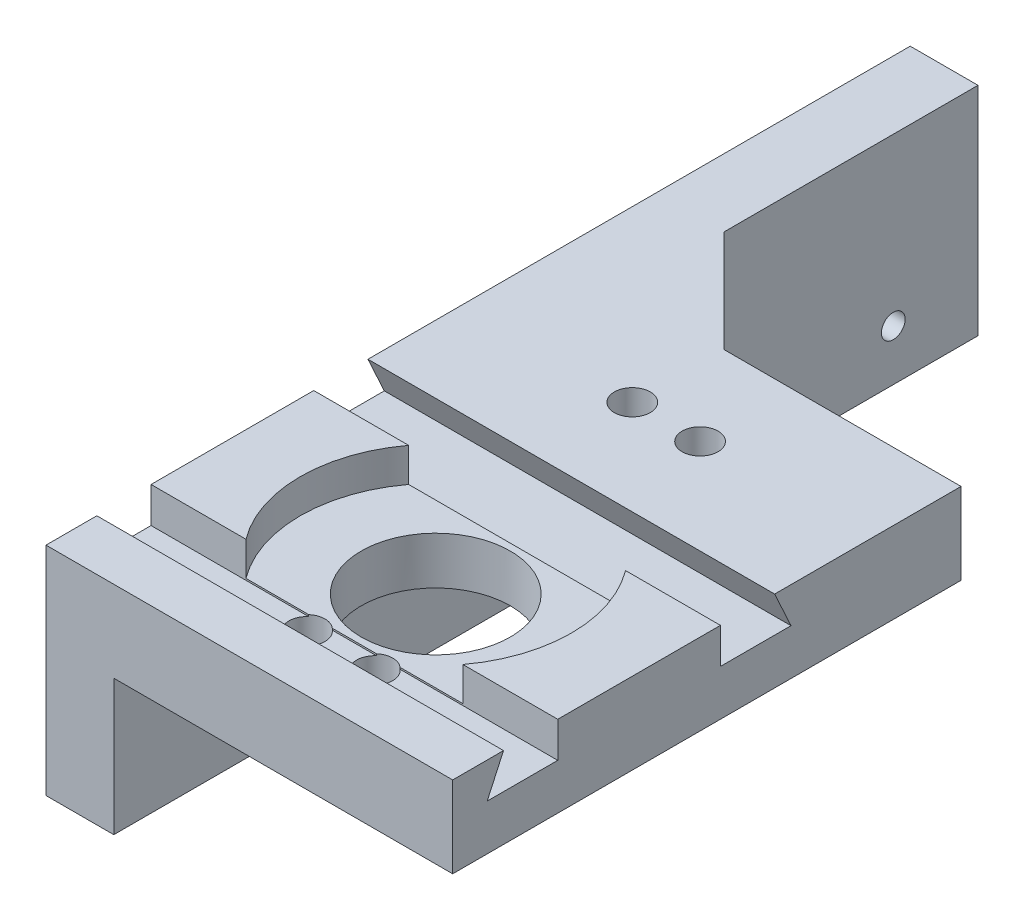
SolidWorks part; units mm, degrees
ref_plane "Front Plane" through (0, 0, 0) normal (0, 0, 1) x (1, 0, 0)
ref_plane "Top Plane" through (0, 0, 0) normal (0, 1, 0) x (1, 0, 0)
ref_plane "Right Plane" through (0, 0, 0) normal (1, 0, 0) x (0, 0, -1)
sketch "Sketch1" plane through (0, 0, 0) normal (0, 1, 0) x (1, 0, 0)
  line L1 (-30, -37.5) -> (30, -37.5)
  line L2 (-30, -37.5) -> (-30, 37.5)
  line L3 (-30, 37.5) -> (30, 37.5)
  line L4 (30, -37.5) -> (30, 37.5)
  line L5 (-30, -37.5) -> (30, 37.5) construction
  line L6 (-30, 37.5) -> (30, -37.5) construction
  point P0 (0, 0)
  dimension "D1" = 75
  dimension "D2" = 60
extrude "Boss-Extrude1" add sketch "Sketch1" along normal blind 12
sketch "Sketch6" plane through (0, 0, 0) normal (0, -1, 0) x (1, 0, 0)
  line L0 (0, 0) -> (0, 24.5997) construction
  line L1 (-10, -28) -> (10, -28)
  line L2 (-10, -28) -> (-10, -20)
  line L3 (-10, -20) -> (10, -20)
  line L4 (10, -28) -> (10, -20)
  line L5 (0, 0) -> (-22.4424, 0) construction
  line L6 (10, 28) -> (10, 20)
  line L7 (-10, 20) -> (10, 20)
  line L8 (-10, 28) -> (-10, 20)
  line L9 (-10, 28) -> (10, 28)
  line L11 (-1.25, -28) -> (1.25, -28)
  line L12 (-1.25, -28) -> (-1.25, 28)
  line L13 (-1.25, 28) -> (1.25, 28)
  line L14 (1.25, -28) -> (1.25, 28)
  circle A0 centre (5, -24) radius 2.4658 construction
  circle A1 centre (-5, -24) radius 2.4658 construction
  circle A2 centre (-5, 24) radius 2.4658 construction
  circle A3 centre (5, 24) radius 2.4658 construction
  point P13 (10, -24)
  dimension "D1" = 10
  dimension "D2" = 5
  dimension "D3" = 4
  dimension "D4" = 48
  dimension "D5" = 2.5
extrude "Boss-Extrude2" add sketch "Sketch6" along normal blind 9 contours L1 L12 L3 L2 | L14 L1 L4 L3 | L14 L7 L6 L9 | L7 L12 L9 L8 region at (-5.625, 0, -24) region at (5.625, 0, -24) region at (-5.625, 0, 24) region at (5.625, 0, 24)
sketch "Sketch3" plane through (0, 12, 0) normal (0, 1, 0) x (1, 0, 0)
  line L0 (-31.5126, 0) -> (79.6914, 0) construction
  line L1 (0, 43.6018) -> (0, -26.5157) construction
  circle A0 centre (-5, 24) radius 2.65
  circle A1 centre (5, 24) radius 2.65
  circle A2 centre (5, -24) radius 2.65
  circle A3 centre (-5, -24) radius 2.65
  circle A4 centre (0, -10) radius 11
  dimension "D1" = 5.3
  dimension "D5" = 22
  dimension "D2" = 10
  dimension "D3" = 48
  dimension "D4" = 14
extrude "Cut-Extrude4" cut sketch "Sketch3" against normal through all
sketch "Sketch5" plane through (0, 12, 0) normal (0, 1, 0) x (1, 0, 0)
  line L0 (20, -10) -> (20, -37.5)
  line L2 (10, -37.5) -> (10, -27.3205)
  line L3 (20, -37.5) -> (10, -37.5)
  line L4 (-10, 7.3205) -> (-10, 37.5)
  line L5 (30, 37.5) -> (-30, 37.5) construction
  line L6 (-20, -10) -> (-20, 37.5)
  line L7 (-20, 37.5) -> (-10, 37.5)
  line L8 (-30, -37.5) -> (30, -37.5) construction
  circle A0 centre (0, -10) radius 20
  circle M2 centre (5, -24) radius 2.65
  circle M3 centre (-5, -24) radius 2.65
  circle M4 centre (0, -10) radius 11
  dimension "D1" = 40
  dimension "D2" = 10
  dimension "D3" = 10
extrude "Cut-Extrude8" cut sketch "Sketch5" against normal blind 5 contours A0 M3 M4 M2 region at (16.8306, 12, 19.7172)
ref_axis "Axis2" through (0, -9, 10) along (0, 1, 0)
ref_plane "Servo Perp Plane" through (0, 0, 10) normal (0, 0, 1) x (1, 0, 0)
ref_plane "Servo Mid Plane" through (0, 0, 0) normal (1, 0, 0) x (0, 1, 0)
sketch "Sketch15" plane through (0, 0, 10) normal (-1, 0, 0) x (0, 0, 1)
  line L0 (0, -12.3146) -> (0, 30.465) construction
  line L1 (20, 30.2968) -> (20, -1.8604) construction
  line L2 (-20, -1.8604) -> (-20, 31.3962) construction
  line L3 (-20, 12) -> (-21.9108, 6.75) construction
  line L5 (-21.9108, 6.75) -> (-12, 6.75)
  line L6 (-12, 6.75) -> (-12, 12)
  line L7 (-12, 12) -> (-20, 12)
  line L8 (12, 12) -> (20, 12)
  line L9 (12, 6.75) -> (12, 12)
  line L10 (21.9108, 6.75) -> (12, 6.75)
  line L11 (20, 12) -> (21.9108, 6.75) construction
  line L12 (-20, 12) -> (-22.4108, 6.75)
  line L13 (-22.4108, 6.75) -> (-21.9108, 6.75)
  line L14 (20, 12) -> (22.4108, 6.75)
  line L15 (22.4108, 6.75) -> (21.9108, 6.75)
  line L16 (-47.5, 12) -> (27.5, 12) construction
  line L17 (0, -10.2052) -> (0, 10.2052) construction
  dimension "D1" = 40
  dimension "D2" = 5.25
  dimension "D3" = 70
  dimension "D5" = 0.5
  dimension "D4" = 8
extrude "Dove Cut" cut sketch "Sketch15" against normal through all and the other way through all
sketch "Sketch8" plane through (-30, 30, 0) normal (1, 0, 0) x (0, 1, 0)
  line L1 (-30, 37.5) -> (-50, 37.5)
  line L2 (-30, 37.5) -> (-30, -37.5)
  line L3 (-30, -90) -> (-50, -90)
  line L4 (-50, 37.5) -> (-50, -90)
  line L8 (-18, 37.5) -> (-30, 37.5) construction
  line L10 (-19.7948, 10) -> (-40.2052, 10) construction
  line L11 (-30, -37.5) -> (-30, 37.5) construction
  line L12 (-18, -37.5) -> (-18, -10) construction
  line L13 (-30, -37.5) -> (-18, -37.5)
  line L15 (-30, -90) -> (-18, -90)
  line L16 (-18, -37.5) -> (-18, -90)
  dimension "D1" = 20
  dimension "D3" = 100
extrude "Boss-Extrude3" add sketch "Sketch8" along normal blind 10
chamfer "Chamfer1" distance 15 angle 45 1 edges at (-20, 6, -37.5)
sketch "Sketch16" plane through (-20, 0, 0) normal (1, 0, 0) x (0, 0, -1)
  line L0 (77.5, -12.5) -> (32.5, -12.5) construction
  line L1 (55, -12.5) -> (55, 24.6929) construction
  line L2 (57.5, 5) -> (52.5, 5) construction
  line L3 (57.5, 3.25) -> (52.5, 3.25)
  line L4 (57.5, 6.75) -> (52.5, 6.75)
  line L6 (-10, 10.2052) -> (-10, -10.2052) construction
  line L7 (-37.5, -20) -> (90, -20) construction
  circle A0 centre (77.5, -12.5) radius 1.75
  circle A1 centre (32.5, -12.5) radius 1.75
  arc A2 (57.5, 3.25) -> (57.5, 6.75) centre (57.5, 5) ccw
  arc A3 (52.5, 6.75) -> (52.5, 3.25) centre (52.5, 5) ccw
  point P8 (55, 5)
  dimension "D1" = 3.5
  dimension "D2" = 45
  dimension "D3" = 65
  dimension "D4" = 17.5
  dimension "D5" = 5
  dimension "D6" = 7.5
extrude "Cut-Extrude9" cut sketch "Sketch16" against normal through all contours A0 | A1 region at (-20, -12.5, -77.5) region at (-20, -12.5, -32.5)
equation "\"DoveAngle\"=70"
equation "\"SweepCircleRadius\"=40"
equation "\"D1@Sketch5\"=\"SweepCircleRadius\""
equation "\"D1@Sketch15\"=\"SweepCircleRadius\""
equation "\"D3@Sketch15\"=\"DoveAngle\""
